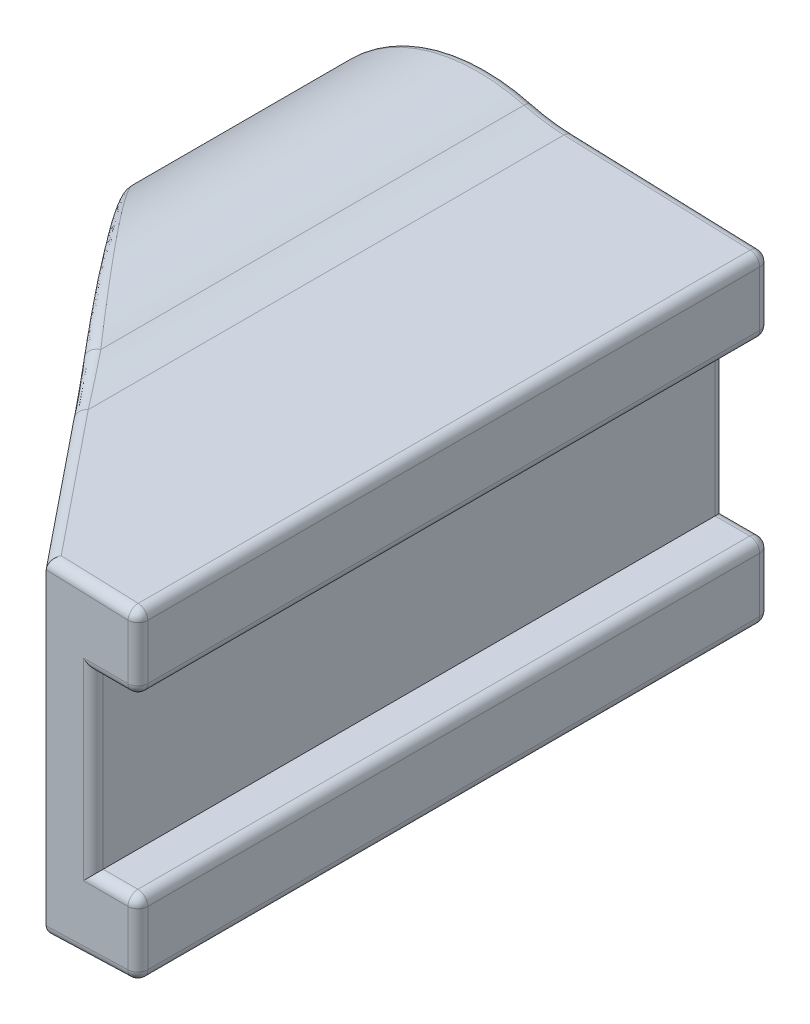
SolidWorks part; units mm, degrees
material "2024-T4"
ref_plane "Front Plane" through (0, 0, 0) normal (0, 0, 1) x (1, 0, 0)
ref_plane "Top Plane" through (0, 0, 0) normal (0, 1, 0) x (1, 0, 0)
ref_plane "Right Plane" through (0, 0, 0) normal (1, 0, 0) x (0, 0, -1)
sketch "Sketch1" plane through (0, 0, 0) normal (0, 0, 1) x (1, 0, 0)
  line L0 (34.6971, 67.6838) -> (113.7, 64.925)
  line L1 (113.7, 64.925) -> (113.7, -64.925)
  line L2 (113.7, -64.925) -> (34.6971, -67.6838)
  arc A0 (18.6136, 70.0698) -> (18.6136, -70.0698) centre (0, 0) ccw
  arc A1 (34.6971, -67.6838) -> (18.6136, -70.0698) centre (37.2273, -140.1397) ccw
  arc A2 (18.6136, 70.0698) -> (34.6971, 67.6838) centre (37.2273, 140.1397) ccw
  point P5 (113.7, 0)
  dimension "D1" = 145
  dimension "D4" = 72.5
  dimension "D2" = 129.85
  dimension "D3" = 113.7
  dimension "D5" = 92
  dimension "D6" = 92
extrude "Boss-Extrude2" add sketch "Sketch1" along normal blind 254.9 contours L0 L1 L2 A1 A0 A2
sketch "Sketch2" plane through (0, 0, 0) normal (0, 1, 0) x (1, 0, 0)
  line L0 (76.7, -254.9) -> (-72.5, -68.8)
  line L1 (113.7, -254.9) -> (113.7, 0) construction
  line L2 (113.7, -254.9) -> (113.7, 0) construction
  line L3 (113.7, -254.9) -> (76.7, -254.9)
  line L4 (113.7, 0) -> (-72.5, 0) construction
  line L5 (-72.5, 0) -> (-72.5, -68.8) construction
  line L6 (-72.5, 0) -> (-72.5, -254.9) construction
  line L7 (-72.5, -68.8) -> (-237.6416, -215.3365)
  line L8 (-237.6416, -215.3365) -> (-172.936, -393.1763)
  line L9 (-172.936, -393.1763) -> (76.7, -254.9)
  dimension "D1" = 68.8
  dimension "D2" = 37
extrude "Cut-Extrude1" cut sketch "Sketch2" against normal mid plane 200 contours L0 L7 L8 L9
sketch "Sketch3" plane through (0, 0, 0) normal (0, 0, -1) x (-1, 0, 0)
  circle A0 centre (0, 0) radius 61.5
  dimension "D1" = 123
extrude "Cut-Extrude2" cut sketch "Sketch3" against normal blind 400
sketch "Sketch4" plane through (113.7, 0, 0) normal (1, 0, 0) x (0, 0, -1)
  line L0 (0, 64.925) -> (0, -64.925) construction
  line L1 (0, -34.925) -> (-254.9, -34.925)
  line L2 (0, -34.925) -> (0, 34.925)
  line L3 (0, 34.925) -> (-254.9, 34.925)
  line L4 (-254.9, -34.925) -> (-254.9, 34.925)
  line L5 (-254.9, 64.925) -> (-254.9, -64.925) construction
  line L7 (-254.9, -64.925) -> (0, -64.925) construction
  dimension "D1" = 69.85
  dimension "D2" = 30
extrude "Cut-Extrude3" cut sketch "Sketch4" against normal blind 18
fillet "Fillet1" radius 4 28 edges at (55.6985, -66.9505, 228.7045) (26.5883, -68.4245, 192.3947) (-72.5, 0, 68.8) (26.5883, 68.4245, 192.3947) (74.1985, 66.3044, 0) (26.5883, 68.4245, 0) (-72.5, 0, 0) (26.5883, -68.4245, 0) (-61.5, 0, 82.5205) (55.6985, 66.9505, 228.7045) (95.2, 65.571, 254.9) (95.2, -65.571, 254.9) (113.7, 49.925, 254.9) (113.7, -49.925, 254.9) (113.7, 64.925, 127.45) (113.7, -49.925, 0) (113.7, 49.925, 0) (74.1985, -66.3044, 0) (113.7, -64.925, 127.45) (-61.5, 0, 0) (104.7, 34.925, 254.9) (95.7, 0, 254.9) (104.7, -34.925, 254.9) (113.7, 34.925, 127.45) (113.7, -34.925, 127.45) (104.7, -34.925, 0) (104.7, 34.925, 0) (95.7, 0, 0)
